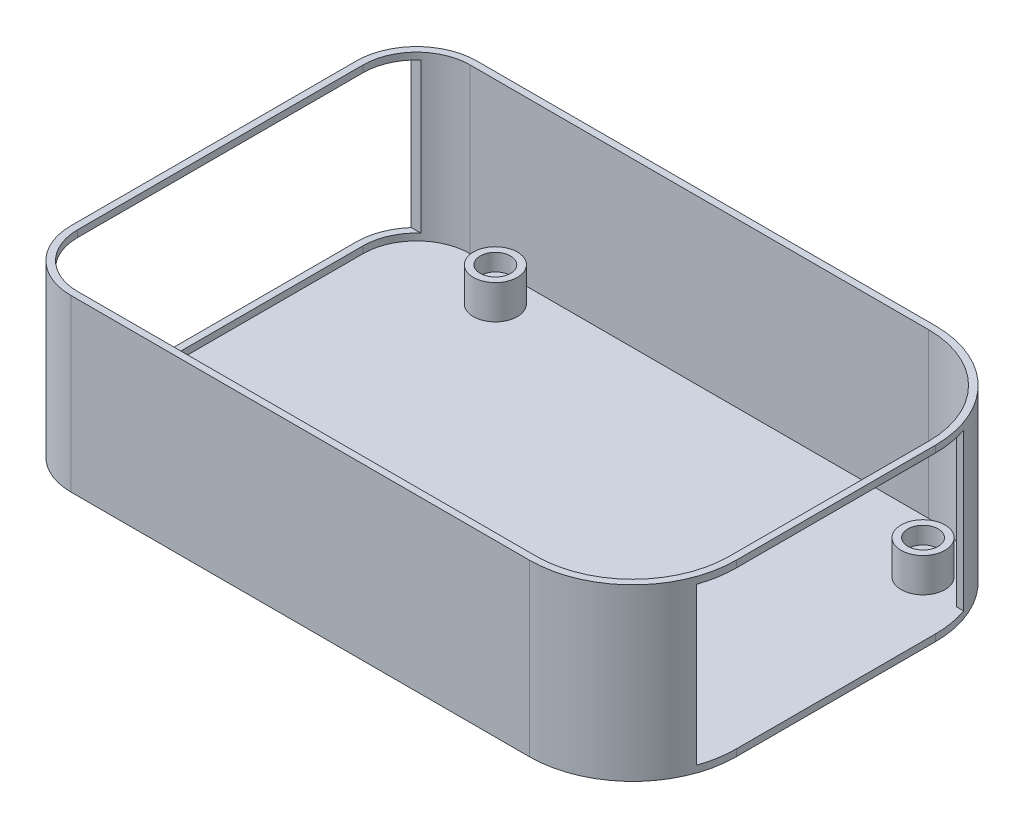
SolidWorks part; units mm, degrees
note: The reader was unsure of these and kept them because the rebuilt part matched: shared geometry of "Sketch1<3>", "Sketch1<4>".
ref_plane "Front Plane" through (0, 0, 0) normal (0, 0, 1) x (1, 0, 0)
ref_plane "Top Plane" through (0, 0, 0) normal (0, 1, 0) x (1, 0, 0)
ref_plane "Right Plane" through (0, 0, 0) normal (1, 0, 0) x (0, 0, -1)
sketch "Sketch1" plane through (0, 0, 0) normal (0, 1, 0) x (1, 0, 0)
  line L0 (0, -45.6209) -> (0, 41.7979) construction
  line L1 (-55.5578, 0) -> (52.9913, 0) construction
  line L2 (-44.68, 20.955) -> (-44.68, -20.955)
  line L3 (-36.83, 27.305) -> (30.48, 27.305) construction
  line L4 (-43.18, 20.955) -> (-43.18, -20.955) construction
  line L5 (-36.83, -27.305) -> (30.48, -27.305) construction
  line L6 (43.18, 14.605) -> (43.18, -14.605) construction
  line L7 (-43.18, 27.305) -> (43.18, -27.305) construction
  line L8 (-43.18, -27.305) -> (43.18, 27.305) construction
  line L9 (-36.83, -28.805) -> (30.48, -28.805)
  line L10 (44.68, 14.605) -> (44.68, -14.605)
  line L11 (-36.83, 28.805) -> (30.48, 28.805)
  line L12 (-36.83, 29.805) -> (30.48, 29.805)
  line L13 (45.68, 14.605) -> (45.68, -14.605)
  line L14 (-36.83, -29.805) -> (30.48, -29.805)
  line L15 (-45.68, 20.955) -> (-45.68, -20.955)
  circle A0 centre (-28.57, 24.265) radius 2.225
  circle A1 centre (37.53, 20.955) radius 2.225
  circle A2 centre (37.53, -20.955) radius 2.225
  circle A3 centre (-28.57, -24.125) radius 2.225
  arc A4 (30.48, 27.305) -> (43.18, 14.605) centre (30.48, 14.605) cw construction
  arc A5 (30.48, -27.305) -> (43.18, -14.605) centre (30.48, -14.605) ccw construction
  arc A6 (-43.18, -20.955) -> (-36.83, -27.305) centre (-36.83, -20.955) ccw construction
  arc A7 (-36.83, 27.305) -> (-43.18, 20.955) centre (-36.83, 20.955) ccw construction
  arc A8 (-36.83, 28.805) -> (-44.68, 20.955) centre (-36.83, 20.955) ccw
  arc A9 (-44.68, -20.955) -> (-36.83, -28.805) centre (-36.83, -20.955) ccw
  arc A10 (30.48, -28.805) -> (44.68, -14.605) centre (30.48, -14.605) ccw
  arc A11 (30.48, 28.805) -> (44.68, 14.605) centre (30.48, 14.605) cw
  arc A12 (30.48, 29.805) -> (45.68, 14.605) centre (30.48, 14.605) cw
  arc A13 (30.48, -29.805) -> (45.68, -14.605) centre (30.48, -14.605) ccw
  arc A14 (-45.68, -20.955) -> (-36.83, -29.805) centre (-36.83, -20.955) ccw
  arc A15 (-36.83, 29.805) -> (-45.68, 20.955) centre (-36.83, 20.955) ccw
  circle A16 centre (-28.57, 24.265) radius 3.225
  circle A17 centre (-28.57, -24.125) radius 3.225
  circle A18 centre (37.53, -20.955) radius 3.225
  circle A19 centre (37.53, 20.955) radius 3.225
  point P5 (0, 0)
  dimension "D3" = 4.45
  dimension "D4" = 66.1
  dimension "D5" = 48.39
  dimension "D6" = 14.61
  dimension "D7" = 3.18
  dimension "D8" = 12.7
  dimension "D10" = 6.35
  dimension "D11" = 41.91
  dimension "D13" = 1
  dimension "D1" = 54.61
  dimension "D2" = 86.36
  dimension "D12" = 1
  dimension "D9" = 1.5
extrude "Boss-Extrude1" add sketch "Sketch1" along normal blind 25 contours L12 A15 L15 A14 L14 A13 L13 A12 L11 A11 L10 A10 L9 A9 L2 A8
extrude "Boss-Extrude2" add sketch "Sketch1<3>" along normal blind 1 contours L3 A7 L4 A6 L5 A5 L6 A4 A0 A1 A2 A3 | A0 | A11 L11 A8 L2 A9 L9 A10 L10 A7 L3 A4 L6 A5 L5 A6 L4 | A1 | A2 | A3 | L3 A16 A0 | L5 A17 A3 | A5 A18 A2 | A4 A19 A1
sketch "Sketch1<3>" plane through (0, 0, 0) normal (0, 1, 0) x (1, 0, 0) same geometry as "Sketch1"
extrude "Boss-Extrude3" add sketch "Sketch1<4>" along normal blind 6 contours A16 A0 | A0 | A17 A3 | A1 | A19 A1 | A2 | A18 A2
sketch "Sketch1<4>" plane through (0, 0, 0) normal (0, 1, 0) x (1, 0, 0) same geometry as "Sketch1"
sketch "Sketch2" plane through (0, 6, 0) normal (0, 1, 0) x (1, 0, 0)
  circle A0 centre (-28.57, 24.265) radius 2.225
  circle A1 centre (-28.57, -24.125) radius 2.225
  circle A2 centre (37.53, -20.955) radius 2.225
  circle A3 centre (37.53, 20.955) radius 2.225
  dimension "D1" = 4.45
extrude "Cut-Extrude1" cut sketch "Sketch2" against normal blind 2.5
sketch "Sketch3" plane through (45.68, 0, 0) normal (1, 0, 0) x (0, 0, -1)
  line L0 (-14.605, 25) -> (-14.605, 0) construction
  line L9 (-19.605, 24) -> (19.605, 24)
  line L10 (-19.605, 24) -> (-19.605, 1)
  line L11 (-19.605, 1) -> (19.605, 1)
  line L12 (19.605, 24) -> (19.605, 1)
  line L13 (14.605, 25) -> (14.605, 0) construction
  line L14 (14.605, 25) -> (-14.605, 25) construction
  line L15 (14.605, 0) -> (-14.605, 0) construction
  dimension "D1" = 5
  dimension "D2" = 5
  dimension "D3" = 1
  dimension "D4" = 1
extrude "Cut-Extrude2" cut sketch "Sketch3" against normal blind 4
sketch "Sketch4" plane through (-45.68, 0, 0) normal (-1, 0, 0) x (0, 0, 1)
  line L1 (-26.805, 24) -> (26.805, 24)
  line L2 (-26.805, 24) -> (-26.805, 2)
  line L3 (-26.805, 2) -> (26.805, 2)
  line L4 (26.805, 24) -> (26.805, 2)
  line L6 (-20.955, 25) -> (20.955, 25) construction
  line L7 (-20.955, 0) -> (20.955, 0) construction
  line L8 (-29.805, 25) -> (-29.805, 0) construction
  line L9 (29.805, 25) -> (29.805, 0) construction
  dimension "D1" = 3
  dimension "D2" = 3
  dimension "D3" = 1
  dimension "D4" = 2
extrude "Cut-Extrude3" cut sketch "Sketch4" against normal blind 7
